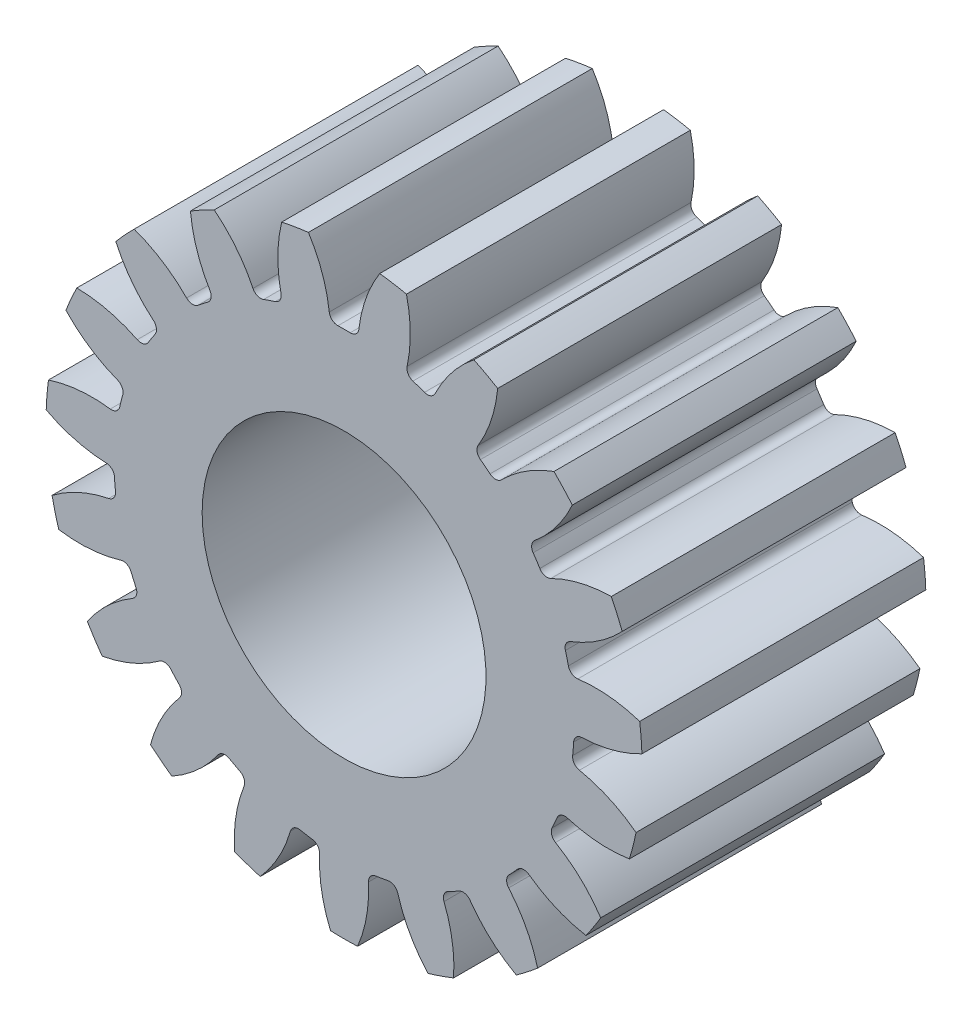
SolidWorks part; units mm, degrees
ref_plane "Front Plane" through (0, 0, 0) normal (0, 0, 1) x (1, 0, 0)
ref_plane "Top Plane" through (0, 0, 0) normal (0, 1, 0) x (1, 0, 0)
ref_plane "Right Plane" through (0, 0, 0) normal (1, 0, 0) x (0, 0, -1)
sketch "Sketch2" plane through (0, 0, 0) normal (0, 0, 1) x (1, 0, 0)
  circle A0 centre (0, 0) radius 9.5 construction
  circle A1 centre (0, 0) radius 10.5
  dimension "D1" = 19
  dimension "D2" = 21
extrude "Boss-Extrude1" add sketch "Sketch2" along normal mid plane 10 contours A1
sketch "Sketch3" plane through (0, 0, 0) normal (0, 0, 1) x (1, 0, 0)
  line L0 (0, 10.5) -> (0, 0) construction
  line L1 (0, 0) -> (3.4093, 9.9311) construction
  line L2 (0, 0) -> (1.7282, 10.3568) construction
  line L3 (-0.4967, 8.0848) -> (0, 0) construction
  line L4 (-0.7845, 9.4676) -> (0.7845, 9.4676) construction
  line L5 (0.7845, 9.4676) -> (2.3321, 9.2093) construction
  line L6 (-1.1378, 10.4382) -> (0, 7.3121) construction
  circle A0 centre (0, 0) radius 8.5 construction
  arc A1 (0.4967, 8.0848) -> (-0.4967, 8.0848) centre (0, 0) ccw
  circle A2 centre (0, 0) radius 10.5 construction
  circle A3 centre (0, 0) radius 9.5 construction
  arc A4 (-1.2558, 10.4246) -> (-0.4967, 8.0848) centre (-5.4136, 7.7827) cw
  arc A5 (1.2558, 10.4246) -> (0.4967, 8.0848) centre (5.4136, 7.7827) ccw
  arc A6 (1.2558, 10.4246) -> (-1.2558, 10.4246) centre (0, 0) ccw
  dimension "D4" = 19
  dimension "D1" = 18.947
  dimension "D3" = 2.4
  dimension "D5" = 20
extrude "Cut-Extrude1" cut sketch "Sketch3" against normal through all both and the other way through all
fillet "Fillet1" radius 0.3 2 edges at (0.4967, 8.0848, 0) (-0.4967, 8.0848, 0)
ref_axis "Axis1" through (0, 0, -11) along (0, 0, 1)
pattern_circular "CirPattern1" count 19 over 360 about axis through (0, 0, -11) along (0, 0, 1) of "Cut-Extrude1", "Fillet1"
sketch "Sketch4" plane through (0, 0, -5) normal (0, 0, -1) x (-1, 0, 0)
  circle A1 centre (0, 0) radius 5
  dimension "D1" = 10
extrude "Cut-Extrude3" cut sketch "Sketch4" against normal blind 10
equation "\"Module\" = 1"
equation "\"Number of teeth\" = 19"
equation "\"pressure angle\"= 20"
equation "\"D1@Sketch2\"=\"Module\"*\"Number of teeth\""
equation "\"D2@Sketch2\"=(\"Number of teeth\"+2) *\"Module\""
equation "\"D1@Sketch3\"=360 /\"Number of teeth\""
equation "\"D2@Sketch3\"=\"Module\"*2"
equation "\"D3@Sketch3\"=\"Module\" *if( \"Module\"=> 1.25,2.25,2.4)"
equation "\"D5@Sketch3\"=\"pressure angle\""
equation "\"D4@Sketch3\"=\"Module\"*\"Number of teeth\""
equation "\"D1@CirPattern1\"=\"Number of teeth\""
equation "\"D1@Fillet1\"=0.3 *\"Module\""
